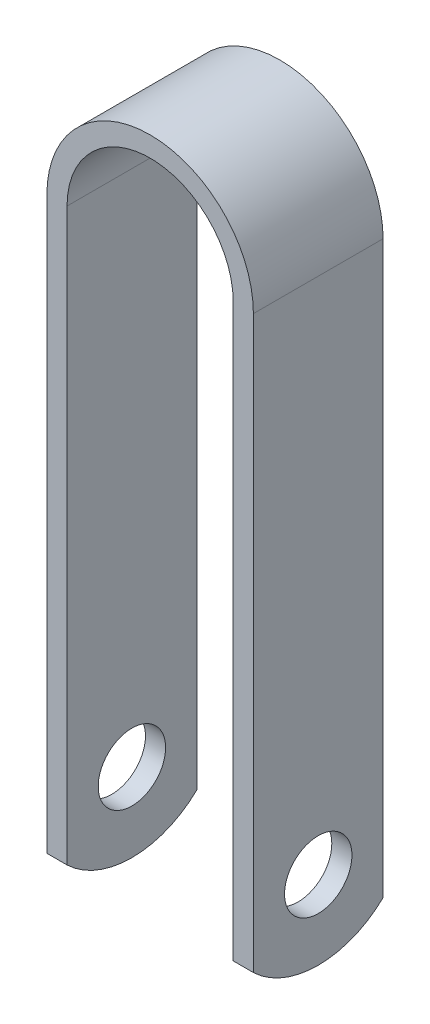
SolidWorks part; units mm, degrees
ref_plane "Front Plane" through (0, 0, 0) normal (0, 0, 1) x (1, 0, 0)
ref_plane "Top Plane" through (0, 0, 0) normal (0, 1, 0) x (1, 0, 0)
ref_plane "Right Plane" through (0, 0, 0) normal (1, 0, 0) x (0, 0, -1)
sketch "Sketch1" plane through (0, 0, 0) normal (0, 0, 1) x (1, 0, 0)
  line L0 (0, -8.0606) -> (0, 23.3641) construction
  line L1 (-18.3408, 0) -> (22.4296, 0) construction
  line L2 (0, 0) -> (2.9845, 0) construction
  line L3 (2.9845, 0) -> (2.9845, 88.4682) construction
  line L4 (0, 0) -> (0, 88.4682)
  line L5 (27.6225, 0) -> (27.6225, 88.4682)
  line L6 (27.6225, 0) -> (30.607, 0)
  line L7 (30.607, 0) -> (30.607, 88.4682)
  line L8 (2.9845, 88.4682) -> (2.9845, 0)
  line L9 (2.9845, 0) -> (0, 0)
  arc A0 (0, 88.4682) -> (30.607, 88.4682) centre (15.3035, 88.4682) cw
  arc A1 (2.9845, 88.4682) -> (27.6225, 88.4682) centre (15.3035, 88.4682) cw
  point P15 (15.3035, 103.7717)
  point P16 (15.3035, 100.7872)
  dimension "D1" = 30.607
  dimension "D2" = 2.9845
  dimension "D3" = 2.9845
  dimension "D4" = 103.7717
  dimension "D5" = 2.9845
extrude "Boss-Extrude1" add sketch "Sketch1" along normal mid plane 19.2278
sketch "Sketch2" plane through (30.607, 0, 0) normal (1, 0, 0) x (0, 0, -1)
  line L0 (-9.6139, 0) -> (-9.6139, 88.4682) construction
  line L1 (9.6139, 0) -> (9.6139, 88.4682) construction
  line L2 (-9.6139, 3.8735) -> (-9.6139, 0)
  line L3 (-9.6139, 0) -> (9.6139, 0)
  line L4 (9.6139, 0) -> (9.6139, 3.8735)
  arc A0 (-9.6139, 3.8735) -> (9.6139, 3.8735) centre (0, 13.8674) ccw
  circle A1 centre (0, 11.6395) radius 4.9974
  line M3 (9.6139, 0) -> (9.6139, 88.4682)
  line M5 (-9.6139, 88.4682) -> (-9.6139, 0)
  line M6 (-9.6139, 0) -> (9.6139, 0)
  dimension "D1" = 9.9949
  dimension "D2" = 11.6395
  dimension "D3" = 3.8735
extrude "Cut-Extrude1" cut sketch "Sketch2" against normal through all both and the other way through all contours A1
extrude "Cut-Extrude2" cut sketch "Sketch2<3>" against normal through all both contours A0 M5 M6 | A0 L3 M3 region at (30.607, 1.1277, 7.2827) region at (30.607, 1.1277, -7.2827)
sketch "Sketch2<3>" plane through (30.607, 0, 0) normal (1, 0, 0) x (0, 0, -1) same geometry as "Sketch2"
